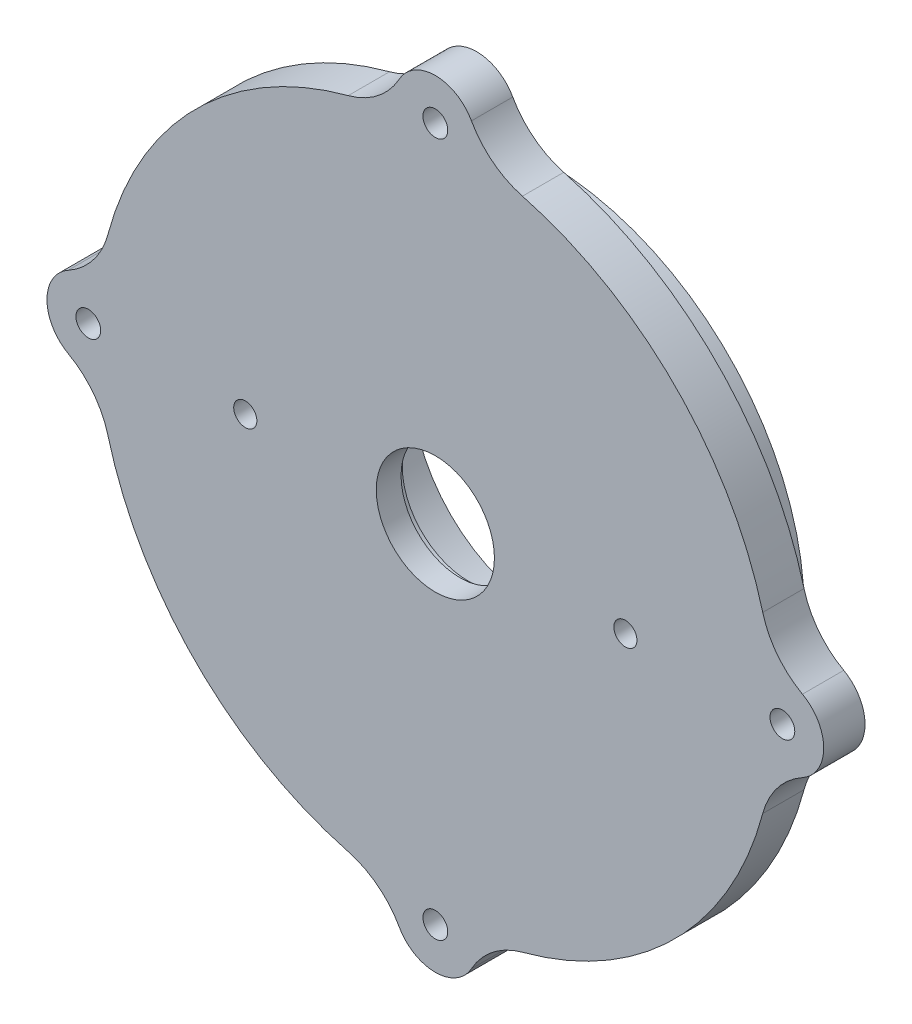
SolidWorks part; units mm, degrees
ref_plane "Ön Düzlem" through (0, 0, 0) normal (0, 0, 1) x (1, 0, 0)
ref_plane "Üst Düzlem" through (0, 0, 0) normal (0, 1, 0) x (1, 0, 0)
ref_plane "Sağ Düzlem" through (0, 0, 0) normal (1, 0, 0) x (0, 0, -1)
sketch "Çizim1" plane through (0, 0, 0) normal (0, 0, 1) x (1, 0, 0)
  circle A0 centre (0, 0) radius 16.1
  circle A1 centre (0, 0) radius 22.5
  circle A2 centre (0, 0) radius 31.4
  circle A3 centre (0, 0) radius 29.425
  dimension "D1" = 32.2
  dimension "D2" = 45
  dimension "D3" = 62.8
  dimension "D4" = 58.85
extrude "Yükseklik-Ekstrüzyon1" add sketch "Çizim1" along normal blind 8.25 contours A1 A0 | A2 A3 region at (-21.8636, 0, 0) region at (-30.5119, 0, 0)
sketch "Çizim2" plane through (0, 0, 8.25) normal (0, 0, 1) x (1, 0, 0)
  arc A6 (-10.5408, 39.6218) -> (-39.6218, 10.5408) centre (0, 0) ccw
  circle A7 centre (0, 42) radius 1.5
  arc A8 (4.3706, 44.4286) -> (-4.3706, 44.4286) centre (0, 42) ccw
  arc A9 (-4.3706, 44.4286) -> (-10.5408, 39.6218) centre (-13.1118, 49.2857) cw
  arc A10 (4.3706, 44.4286) -> (10.5408, 39.6218) centre (13.1118, 49.2857) ccw
  arc A11 (44.4286, 4.3706) -> (39.6218, 10.5408) centre (49.2857, 13.1118) cw
  arc A12 (44.4286, -4.3706) -> (44.4286, 4.3706) centre (42, 0) ccw
  circle A13 centre (42, 0) radius 1.5
  arc A14 (44.4286, -4.3706) -> (39.6218, -10.5408) centre (49.2857, -13.1118) ccw
  arc A15 (4.3706, -44.4286) -> (10.5408, -39.6218) centre (13.1118, -49.2857) cw
  arc A16 (-4.3706, -44.4286) -> (4.3706, -44.4286) centre (0, -42) ccw
  circle A17 centre (0, -42) radius 1.5
  arc A18 (-4.3706, -44.4286) -> (-10.5408, -39.6218) centre (-13.1118, -49.2857) ccw
  arc A19 (-44.4286, -4.3706) -> (-39.6218, -10.5408) centre (-49.2857, -13.1118) cw
  arc A20 (-44.4286, 4.3706) -> (-44.4286, -4.3706) centre (-42, 0) ccw
  circle A21 centre (-42, 0) radius 1.5
  arc A22 (-44.4286, 4.3706) -> (-39.6218, 10.5408) centre (-49.2857, 13.1118) ccw
  arc A23 (-39.6218, -10.5408) -> (-10.5408, -39.6218) centre (0, 0) ccw
  arc A24 (10.5408, -39.6218) -> (39.6218, -10.5408) centre (0, 0) ccw
  arc A25 (39.6218, 10.5408) -> (10.5408, 39.6218) centre (0, 0) ccw
  circle A26 centre (0, 0) radius 7.15
  point P0 (0, 0)
  point P17 (0, 0)
  point P48 (0, 0)
  dimension "D1" = 82
  dimension "D2" = 42
  dimension "D7" = 10
  dimension "D8" = 3
  dimension "D9" = 10
  dimension "D10" = 10
  dimension "D12" = 14.3
  dimension "D11" = 4
extrude "Yükseklik-Ekstrüzyon2" add sketch "Çizim2" along normal blind 5
sketch "Çizim7" plane through (0, 0, 8.25) normal (0, 0, -1) x (-1, 0, 0)
  circle A0 centre (0, 0) radius 16.1 construction
  circle A1 centre (0, 0) radius 16.1
extrude "Kes-Ekstrüzyon2" cut sketch "Çizim7" against normal blind 1
sketch "Çizim8" plane through (0, 0, 9.25) normal (0, 0, -1) x (-1, 0, 0)
  circle A0 centre (0, 0) radius 8
  dimension "D1" = 16
extrude "Kes-Ekstrüzyon3" cut sketch "Çizim8" against normal blind 1
sketch "Çizim9" plane through (0, 0, 13.25) normal (0, 0, 1) x (1, 0, 0)
  circle A0 centre (-23, 0) radius 1.4
  circle A1 centre (23, 0) radius 1.4
  point P4 (0, 0)
  point P5 (0, 0)
  point P6 (-13.18, -0.659)
  dimension "D1" = 2.8
  dimension "D2" = 2.8
  dimension "D4" = 23
  dimension "D3" = 46
extrude "Kes-Ekstrüzyon4" cut sketch "Çizim9" against normal blind 25.4 contours A0 | A1
